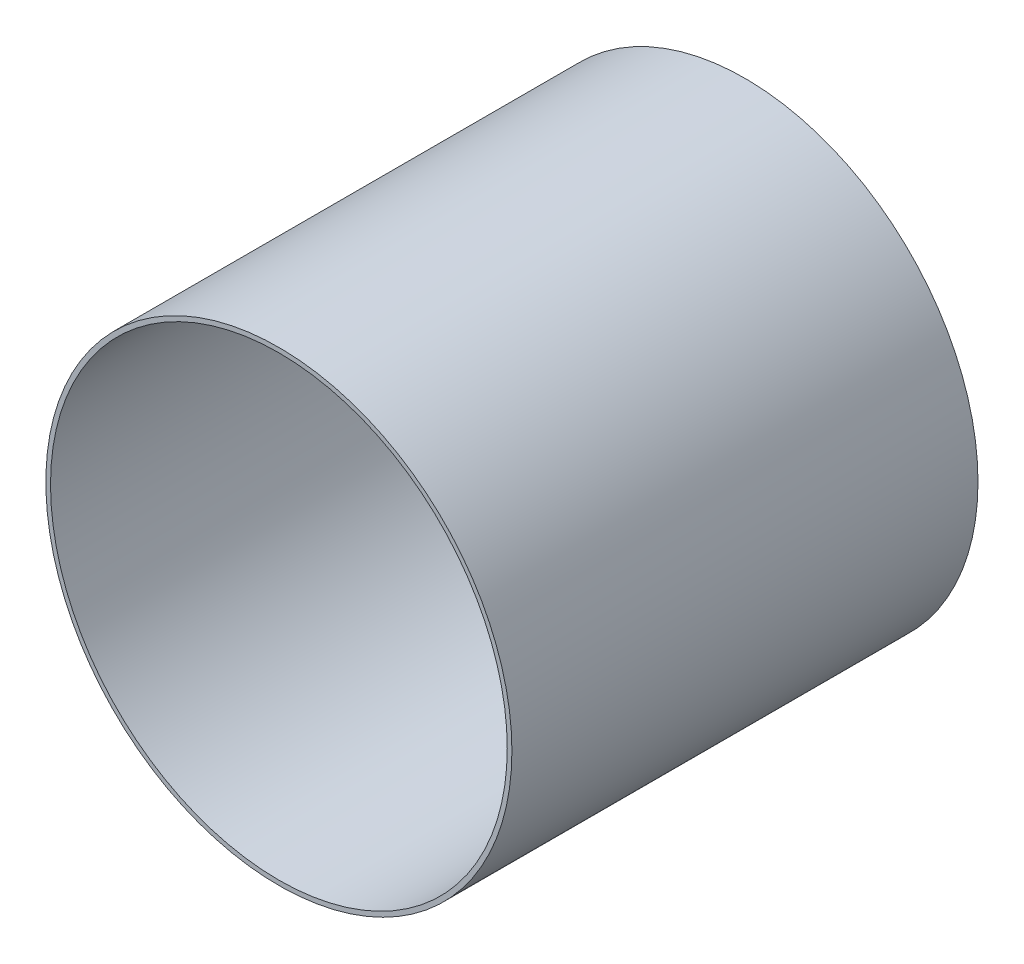
SolidWorks part; units mm, degrees
ref_plane "Front Plane" through (0, 0, 0) normal (0, 0, 1) x (1, 0, 0)
ref_plane "Top Plane" through (0, 0, 0) normal (0, 1, 0) x (1, 0, 0)
ref_plane "Right Plane" through (0, 0, 0) normal (1, 0, 0) x (0, 0, -1)
sketch "Sketch1" plane through (0, 0, 0) normal (0, 0, 1) x (1, 0, 0)
  circle A0 centre (0, 0) radius 150
  circle A1 centre (0, 0) radius 147
  dimension "D2" = 300
  dimension "D1" = 3
extrude "Boss-Extrude1" add sketch "Sketch1" along normal blind 150 and the other way blind 150
equation "\"acTubeOD\"= 300mm"
equation "\"acTubeThickness\"= 3mm"
equation "\"acTubeLength\"= 300mm"
equation "\"D2@Sketch1\"=\"acTubeOD\""
equation "\"D1@Sketch1\"=\"acTubeThickness\""
equation "\"D1@Boss-Extrude1\"=\"acTubeLength\"/2"
equation "\"D2@Boss-Extrude1\"=\"acTubeLength\"/2"
